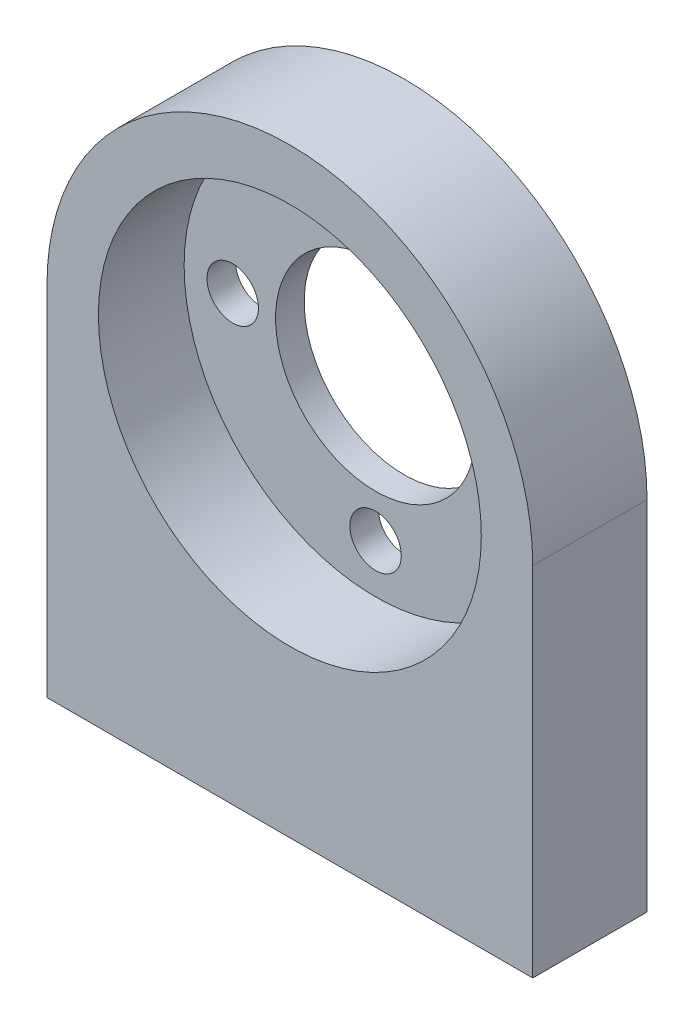
SolidWorks part; units mm, degrees
ref_plane "Plan de face" through (0, 0, 0) normal (0, 0, 1) x (1, 0, 0)
ref_plane "Plan de dessus" through (0, 0, 0) normal (0, 1, 0) x (1, 0, 0)
ref_plane "Plan de droite" through (0, 0, 0) normal (1, 0, 0) x (0, 0, -1)
sketch "Esquisse1" plane through (0, 0, 0) normal (0, 0, 1) x (1, 0, 0)
  line L0 (0, 0) -> (0, 10) construction
  line L1 (-17, 0) -> (17, 0) construction
  line L2 (-17, 0) -> (-17, -25)
  line L3 (-17, -25) -> (17, -25)
  line L4 (17, 0) -> (17, -25)
  circle A0 centre (0, 0) radius 17 construction
  arc A1 (-17, 0) -> (17, 0) centre (0, 0) cw
  circle A2 centre (0, 0) radius 7
  circle A3 centre (0, 10) radius 1.8
  circle A4 centre (10, 0) radius 1.8
  circle A5 centre (0, -10) radius 1.8
  circle A6 centre (-10, 0) radius 1.8
  point P0 (0, 0)
  point P11 (0, 0)
  point P20 (0, 0)
  dimension "D3" = 14
  dimension "D5" = 3.6
  dimension "D1" = 34
  dimension "D2" = 25
  dimension "D4" = 10
  dimension "D6" = 4
extrude "Boss.-Extru.1" add sketch "Esquisse1" along normal blind 8
sketch "Esquisse2" plane through (0, 0, 8) normal (0, 0, 1) x (1, 0, 0)
  circle A0 centre (0, 0) radius 13.4
  dimension "D1" = 26.8
extrude "Enlèv. mat.-Extru.1" cut sketch "Esquisse2" against normal blind 6
sketch "Esquisse3" plane through (0, -25, 0) normal (0, -1, 0) x (1, 0, 0)
  line L0 (-12, 4) -> (12, 4) construction
  line L1 (0, 0) -> (0, 8) construction
  line L2 (-17, 8) -> (17, 8) construction
  line L3 (-17, 8) -> (-17, 0) construction
  circle A0 centre (-12, 4) radius 2
  circle A1 centre (12, 4) radius 2
  point P8 (0, 4)
  point P9 (0, 4)
  dimension "D1" = 4
  dimension "D2" = 5
extrude "Enlèv. mat.-Extru.2" cut sketch "Esquisse3" against normal blind 12
chamfer "Chanfrein1" distance 1 angle 45 2 edges at (12, -25, 2) (-12, -25, 2)
